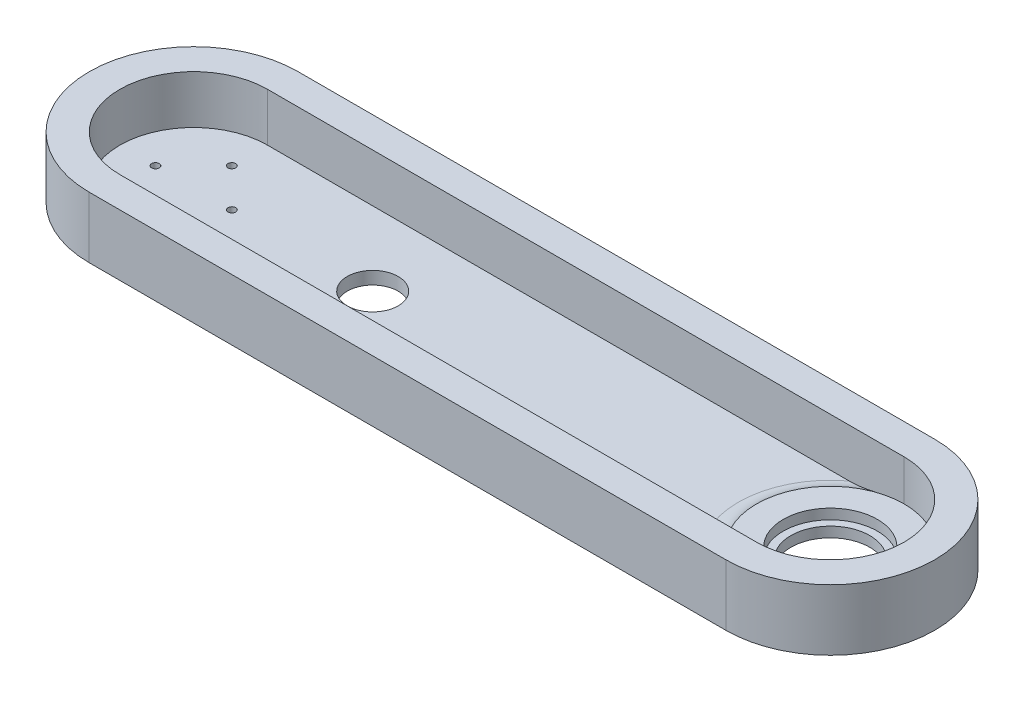
SolidWorks part; units mm, degrees
ref_plane "Front Plane" through (0, 0, 0) normal (0, 0, 1) x (1, 0, 0)
ref_plane "Top Plane" through (0, 0, 0) normal (0, 1, 0) x (1, 0, 0)
ref_plane "Right Plane" through (0, 0, 0) normal (1, 0, 0) x (0, 0, -1)
sketch "Sketch1" plane through (0, 0, 0) normal (0, 1, 0) x (1, 0, 0)
  line L0 (0, 0) -> (250, 0) construction
  line L1 (0, 29) -> (250, 29)
  line L2 (0, -41) -> (250, -41)
  line L3 (0, -29) -> (250, -29)
  line L4 (0, 41) -> (250, 41)
  arc A0 (0, 29) -> (0, -29) centre (0, 0) ccw
  arc A1 (250, -29) -> (250, 29) centre (250, 0) ccw
  arc A2 (0, 41) -> (0, -41) centre (0, 0) ccw
  arc A3 (250, -41) -> (250, 41) centre (250, 0) ccw
  dimension "D1" = 58
  dimension "D3" = 12
  dimension "D2" = 250
extrude "Boss-Extrude1" add sketch "Sketch1" along normal blind 19
extrude "Boss-Extrude2" add sketch "Sketch1<2>" against normal blind 5 contours L3 A1 L1 A0 | L2 A3 L4 A2 A1 L3 A0 L1 region at (125, 0, 0) region at (-37.5802, 0, 0)
sketch "Sketch1<2>" plane through (0, 0, 0) normal (0, 1, 0) x (1, 0, 0) same geometry as "Sketch1"
sketch "Sketch3" plane through (0, 0, 0) normal (0, 1, 0) x (1, 0, 0)
  circle A0 centre (0, 0) radius 15 construction
  circle A1 centre (0, 15) radius 1.5
  circle A2 centre (15, 0) radius 1.5
  circle A3 centre (0, -15) radius 1.5
  circle A4 centre (-15, 0) radius 1.5
  point P14 (0, 0)
  dimension "D1" = 30
  dimension "D2" = 3
  dimension "D3" = 4
extrude "Cut-Extrude1" cut sketch "Sketch3" against normal through all both and the other way through all
sketch "Sketch4" plane through (0, 0, 0) normal (0, 1, 0) x (1, 0, 0)
  circle A0 centre (250, 0) radius 29
extrude "Boss-Extrude3" add sketch "Sketch4" along normal blind 3
sketch "Sketch5" plane through (0, 3, 0) normal (0, 1, 0) x (1, 0, 0)
  circle A0 centre (250, 0) radius 18.5
  dimension "D1" = 37
extrude "Cut-Extrude2" cut sketch "Sketch5" against normal blind 4 contours A0
sketch "Sketch6" plane through (0, -1, 0) normal (0, 1, 0) x (1, 0, 0)
  circle A0 centre (250, 0) radius 15.5
  dimension "D1" = 31
extrude "Cut-Extrude3" cut sketch "Sketch6" against normal through all both and the other way through all
fillet "Fillet1" radius 10 1 edges at (221, 0, 0)
sketch "Sketch7" plane through (0, 0, 0) normal (0, 1, 0) x (1, 0, 0)
  line L0 (0, 0) -> (250, 0) construction
  circle A0 centre (70.3, 0) radius 10
  dimension "D1" = 20
  dimension "D2" = 70.3
extrude "Cut-Extrude4" cut sketch "Sketch7" against normal through all both and the other way through all
